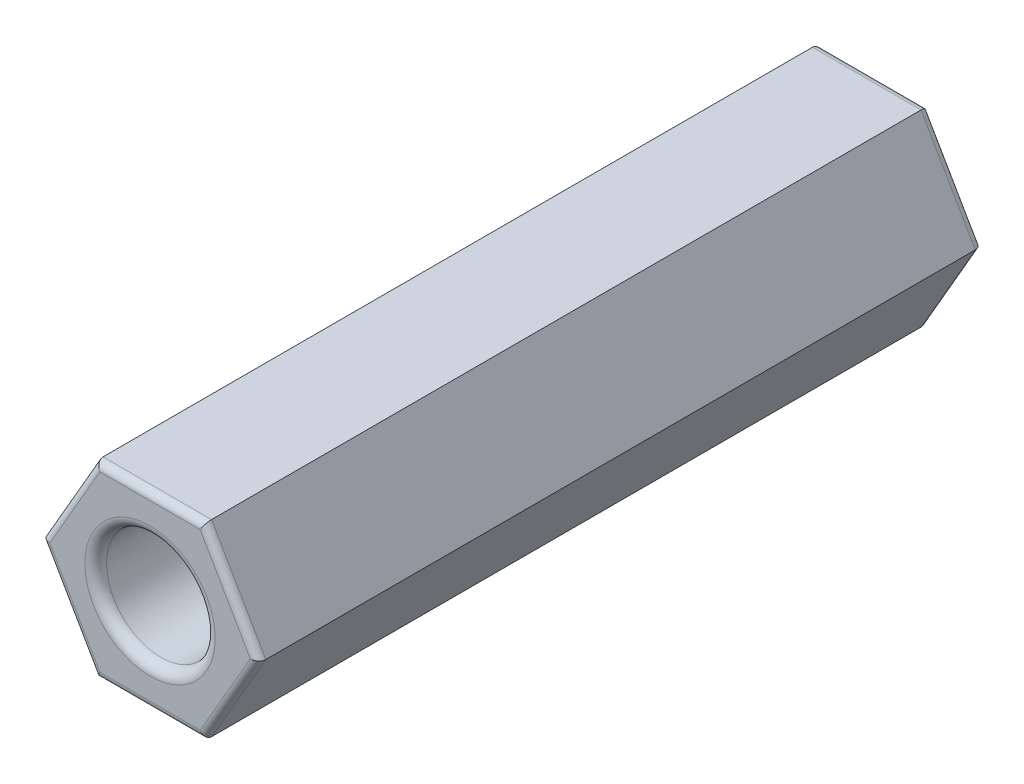
SolidWorks part; units mm, degrees
ref_plane "Front Plane" through (0, 0, 0) normal (0, 0, 1) x (1, 0, 0)
ref_plane "Top Plane" through (0, 0, 0) normal (0, 1, 0) x (1, 0, 0)
ref_plane "Right Plane" through (0, 0, 0) normal (1, 0, 0) x (0, 0, -1)
ref_axis "Axis1" through (0, 0, -5.8251) along (0, 0, 1)
sketch "Sketch1" plane through (0, 0, 0) normal (0, 0, 1) x (1, 0, 0)
  line L1 (3, 0) -> (1.5, 2.5981)
  line L2 (1.5, 2.5981) -> (-1.5, 2.5981)
  line L3 (-1.5, 2.5981) -> (-3, 0)
  line L4 (-3, 0) -> (-1.5, -2.5981)
  line L5 (-1.5, -2.5981) -> (1.5, -2.5981)
  line L6 (1.5, -2.5981) -> (3, 0)
  circle A0 centre (0, 0) radius 2.5981 construction
  circle A1 centre (0, 0) radius 1.5
  dimension "D2" = 3
  dimension "D1" = 6
extrude "Boss-Extrude1" add sketch "Sketch1" along normal blind 20
fillet "Fillet1" radius 0.3 2 edges at (1.5, 0, 0) (1.5, 0, 20)
fillet "Fillet2" radius 0.2 12 edges at (-2.25, 1.299, 20) (-2.25, -1.299, 20) (0, -2.5981, 20) (2.25, -1.299, 20) (2.25, 1.299, 20) (0, 2.5981, 20) (2.25, -1.299, 0) (0, -2.5981, 0) (-2.25, -1.299, 0) (-2.25, 1.299, 0) (0, 2.5981, 0) (2.25, 1.299, 0)
